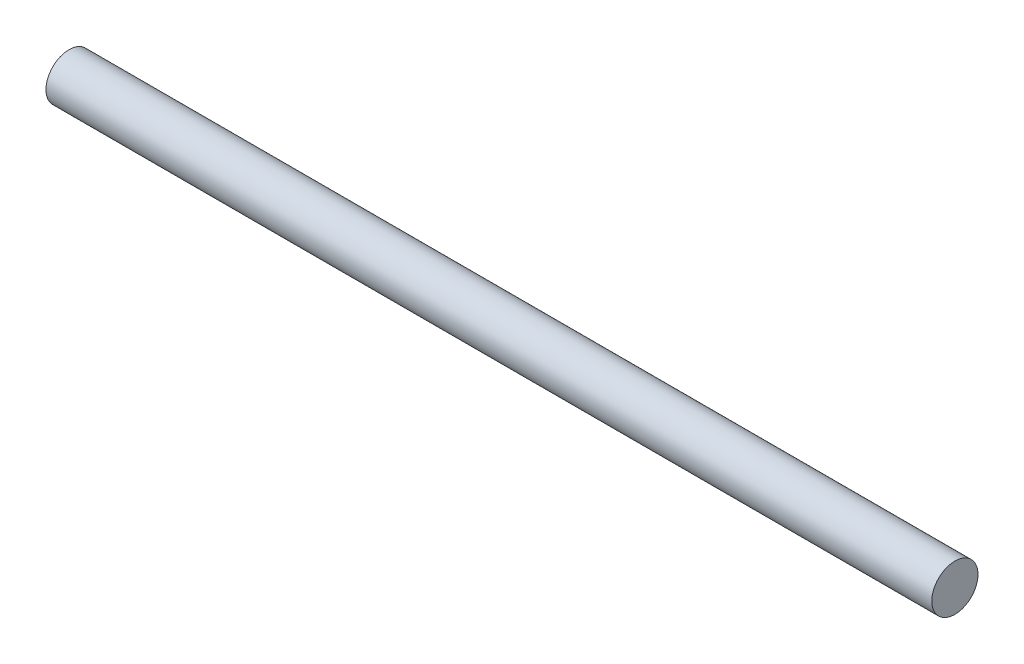
SolidWorks part; units mm, degrees
ref_plane "Front Plane" through (0, 0, 0) normal (0, 0, 1) x (1, 0, 0)
ref_plane "Top Plane" through (0, 0, 0) normal (0, 1, 0) x (1, 0, 0)
ref_plane "Right Plane" through (0, 0, 0) normal (1, 0, 0) x (0, 0, -1)
sketch "Sketch1" plane through (0, 0, 0) normal (1, 0, 0) x (0, 0, -1)
  circle A0 centre (0, 0) radius 6.523
extrude "Boss-Extrude1" add sketch "Sketch1" along normal blind 125 and the other way blind 125
